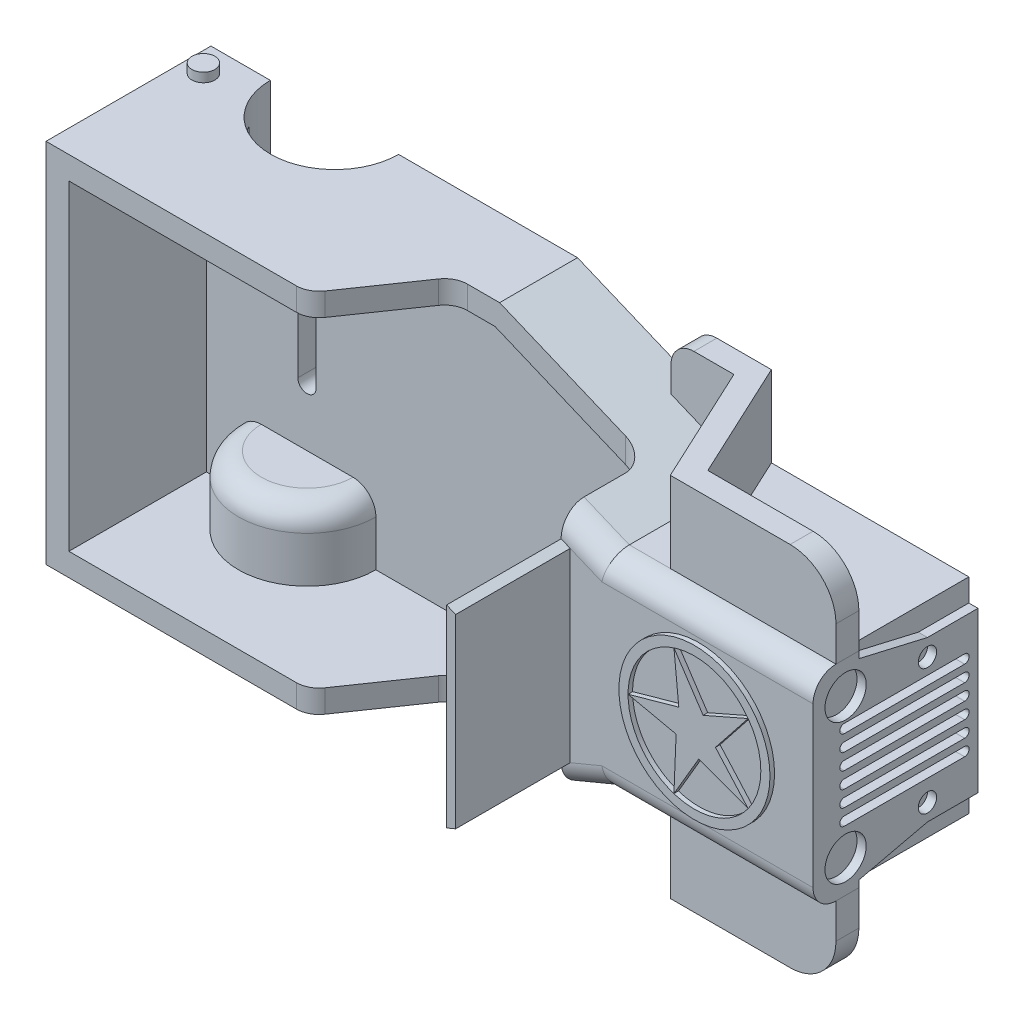
SolidWorks part; units mm, degrees
ref_plane "Front Plane" through (0, 0, 0) normal (0, 0, 1) x (1, 0, 0)
ref_plane "Top Plane" through (0, 0, 0) normal (0, 1, 0) x (1, 0, 0)
ref_plane "Right Plane" through (0, 0, 0) normal (1, 0, 0) x (0, 0, -1)
sketch "Sketch1" plane through (0, 0, 0) normal (0, 0, 1) x (1, 0, 0)
  line L0 (-30, -40) -> (-30, 40)
  line L1 (-30, 40) -> (50, 40)
  line L2 (50, 40) -> (92.3198, 22.3788)
  line L3 (92.3198, 22.3788) -> (137.4114, 22.3788)
  line L4 (137.4114, 22.3788) -> (137.4114, -22.3788)
  line L6 (92.3198, -22.3788) -> (137.4114, -22.3788)
  line L7 (50, -40) -> (92.3198, -22.3788)
  line L8 (-30, -40) -> (50, -40)
  dimension "D1" = 80
  dimension "D2" = 80
extrude "Boss-Extrude1" add sketch "Sketch1" against normal blind 6
sketch "Sketch2" plane through (0, 0, 0) normal (0, 0, 1) x (1, 0, 0)
  line L0 (82.4322, 26.4958) -> (82.4322, -26.4958)
  line L8 (137.4114, 22.3788) -> (92.3198, 22.3788)
  line L9 (92.3198, 22.3788) -> (50, 40)
  line L10 (50, 40) -> (-30, 40)
  line L11 (-30, 40) -> (-30, -40)
  line L12 (-30, -40) -> (50, -40)
  line L13 (50, -40) -> (92.3198, -22.3788)
  line L14 (92.3198, -22.3788) -> (137.4114, -22.3788)
  line L15 (137.4114, -22.3788) -> (137.4114, 22.3788)
  line L16 (137.4114, 22.3788) -> (92.3198, 22.3788)
  line L17 (92.3198, 22.3788) -> (82.4322, 26.4958)
  line L21 (82.4322, -26.4958) -> (92.3198, -22.3788)
  line L22 (92.3198, -22.3788) -> (137.4114, -22.3788)
  line L23 (137.4114, -22.3788) -> (137.4114, 22.3788)
  dimension "D1" = 0
extrude "Boss-Extrude2" add sketch "Sketch2" along normal blind 30
fillet "Fillet1" radius 5 4 edges at (114.8656, 22.3788, 30) (114.8656, -22.3788, 30) (87.376, 24.4373, 30) (87.376, -24.4373, 30)
shell "Shell1" thickness 5 removed face at (82.4322, 4.416, 22.8452)
sketch "Sketch3" plane through (0, 0, 0) normal (0, 0, 1) x (1, 0, 0)
  line L8 (82.4322, 21.0797) -> (82.4322, 26.4958)
  line L9 (82.4322, 26.4958) -> (50, 40)
  line L10 (50, 40) -> (-30, 40)
  line L11 (-30, 40) -> (-30, -40)
  line L12 (-30, -40) -> (50, -40)
  line L13 (50, -40) -> (82.4322, -26.4958)
  line L14 (82.4322, -26.4958) -> (82.4322, -21.0797)
  line L15 (82.4322, -21.0797) -> (82.4322, 21.0797)
  line L16 (82.4322, 21.0797) -> (82.4322, 26.4958)
  line L17 (82.4322, 26.4958) -> (50, 40)
  line L18 (50, 40) -> (-30, 40)
  line L19 (-30, 40) -> (-30, -40)
  line L20 (-30, -40) -> (50, -40)
  line L21 (50, -40) -> (82.4322, -26.4958)
  line L22 (82.4322, -26.4958) -> (82.4322, -21.0797)
  line L40 (77.4322, 21.0797) -> (77.4322, 23.1616)
  line L41 (77.4322, 23.1616) -> (49.0006, 35)
  line L42 (49.0006, 35) -> (-25, 35)
  line L43 (-25, 35) -> (-25, -35)
  line L44 (-25, -35) -> (49.0006, -35)
  line L45 (49.0006, -35) -> (77.4322, -23.1616)
  line L46 (77.4322, -23.1616) -> (77.4322, -21.0797)
  line L47 (77.4322, -21.0797) -> (77.4322, 21.0797)
  line L49 (82.4322, 21.0797) -> (49.0006, 35)
  line L50 (49.0006, 35) -> (-25, 35)
  line L51 (-25, 35) -> (-25, -35)
  line L52 (-25, -35) -> (49.0006, -35)
  line L53 (49.0006, -35) -> (82.4322, -21.0797)
  dimension "D1" = 0
  dimension "D2" = 5
extrude "Boss-Extrude3" add sketch "Sketch3" along normal blind 30
sketch "Sketch4" plane through (0, 0, 0) normal (0, 1, 0) x (1, 0, 0)
  line L0 (82.4322, -30) -> (82.4322, -11)
  line L1 (82.4322, -11) -> (40.3506, -11)
  line L2 (40.3506, -11) -> (27.2574, -30)
  line L3 (-30, -30) -> (50, -30) construction
  line L4 (27.2574, -30) -> (82.4322, -30)
extrude "Cut-Extrude1" cut sketch "Sketch4" against normal through all both and the other way through all
fillet "Fillet2" radius 5 6 edges at (82.4322, -23.7877, 11) (82.4322, 23.7877, 11) (40.3506, -37.5, 11) (40.3506, 37.5, 11) (27.2574, -37.5, 30) (27.2574, 37.5, 30)
sketch "Sketch10" plane through (0, 35, 0) normal (0, -1, 0) x (1, 0, 0)
  line L0 (-25, 0) -> (49.0006, 0) construction
  line L1 (-17.9963, 0) -> (-15.9963, 0)
  line L2 (10.0037, 0) -> (12.0037, 0)
  arc A0 (-15.9963, 0) -> (10.0037, 0) centre (-2.9963, 0) cw
  arc A1 (-17.9963, 0) -> (12.0037, 0) centre (-2.9963, 0) cw
  dimension "D1" = 13
  dimension "D2" = 2
extrude "Boss-Extrude8" add sketch "Sketch10" along normal blind 15
sketch "Sketch13" plane through (0, 40, 0) normal (0, 1, 0) x (1, 0, 0)
  line L0 (10.9614, 6.063) -> (-17.0386, 6.063)
  arc A2 (-17.0386, 6.063) -> (10.9614, 6.063) centre (-3.0386, 6.063) ccw
extrude "Cut-Extrude4" cut sketch "Sketch13" against normal blind 15
sketch "Sketch14" plane through (0, 20, 0) normal (0, -1, 0) x (1, 0, 0)
  line L0 (-15.9963, 0) -> (10.0037, 0)
  arc A0 (10.0037, 0) -> (-15.9963, 0) centre (-2.9963, 0) ccw construction
  arc A1 (10.0037, 0) -> (-15.9963, 0) centre (-2.9963, 0) ccw
extrude "Boss-Extrude10" add sketch "Sketch14" against normal up to vertex (5 mm away) up to point (-15.6576, 25, 0)
fillet "Fillet3" radius 5 1 edges at (-2.9963, 20, 15)
mirror "Mirror1" about plane through (0, 0, 0) normal (0, 1, 0) of "Fillet3", "Boss-Extrude10", "Boss-Extrude8", "Cut-Extrude4"
sketch "Sketch15" plane through (0, -40, 0) normal (0, -1, 0) x (1, 0, 0)
  line L0 (137.4114, 20) -> (104.4438, 20)
  line L1 (137.4114, -6) -> (137.4114, 25) construction
  line L2 (104.4438, 20) -> (92.3198, -6)
  line L3 (92.3198, -6) -> (75.4114, -6)
  line L4 (50, -6) -> (92.3198, -6) construction
  line L5 (137.4114, 25) -> (137.4114, 20)
  line L6 (137.4114, 25) -> (101.2584, 25)
  line L7 (101.2584, 25) -> (89.1344, -1)
  line L8 (89.1344, -1) -> (75.4114, -1)
  line L9 (75.4114, -1) -> (75.4114, -6)
  dimension "D1" = 115
  dimension "D2" = 26
  dimension "D3" = 62
  dimension "D4" = 16.9084
  dimension "D5" = 5
extrude "Boss-Extrude11" add sketch "Sketch15" against normal up to next separate body
fillet "Fillet4" radius 5 1 edges at (75.4114, -40, -3.5)
fillet "Fillet5" radius 10 1 edges at (137.4114, -40, 22.5)
mirror "Mirror6" about plane through (0, 0, 0) normal (0, 1, 0) of bodies 115
sketch "Sketch16" plane through (137.4114, 0, 0) normal (1, 0, 0) x (0, 0, -1)
  line L0 (-30, 0) -> (6, 0) construction
  line L1 (-30, -17.3788) -> (-30, 17.3788) construction
  line L2 (6, -22.3788) -> (6, 22.3788) construction
  line L4 (-20, -22.3788) -> (-20, -20.9143)
  line L5 (-20, -20.9143) -> (-5.0256, -17.436)
  line L6 (-5.0256, -17.436) -> (6, -17.436)
  line L7 (6, -17.436) -> (6, -22.3788)
  line L8 (6, -22.3788) -> (-20, -22.3788)
  circle A1 centre (-22.8997, -15.2785) radius 4.5
  circle A2 centre (-5.0256, -13.7435) radius 2
  dimension "D1" = 4
  dimension "D2" = 9
extrude "Cut-Extrude5" cut sketch "Sketch16" against normal blind 2
mirror "Mirror7" about plane through (0, 0, 0) normal (0, 1, 0) of "Cut-Extrude5"
sketch "Sketch17" plane through (137.4114, 0, 0) normal (1, 0, 0) x (0, 0, -1)
  line L0 (-23.1915, -8.1908) -> (3.0841, -8.1908) construction
  line L1 (-23.1915, -7.2177) -> (3.0841, -7.2177)
  line L2 (-23.1915, -9.164) -> (3.0841, -9.164)
  arc A0 (-23.1915, -7.2177) -> (-23.1915, -9.164) centre (-23.1915, -8.1908) ccw
  arc A1 (3.0841, -9.164) -> (3.0841, -7.2177) centre (3.0841, -8.1908) ccw
  point P2 (-10.0537, -8.1908)
extrude "Cut-Extrude6" cut sketch "Sketch17" against normal blind 2
pattern_linear "LPattern1" count 6 spacing 3.5 along (0, 1, 0) of "Cut-Extrude6"
sketch "Sketch18" plane through (0, 0, -6) normal (0, 0, -1) x (-1, 0, 0)
  line L4 (1.0386, -7.2126) -> (1.0386, 7.2126)
  line L5 (5.0386, -7.2126) -> (5.0386, 7.2126)
  line L14 (-108.4499, -7.2126) -> (-108.4499, 7.2126)
  line L15 (-112.4499, -7.2126) -> (-112.4499, 7.2126)
  arc A0 (1.0386, -7.2126) -> (5.0386, -7.2126) centre (3.0386, -7.2126) ccw
  arc A1 (5.0386, 7.2126) -> (1.0386, 7.2126) centre (3.0386, 7.2126) ccw
  arc A2 (-108.4499, -7.2126) -> (-112.4499, -7.2126) centre (-110.4499, -7.2126) cw
  arc A3 (-112.4499, 7.2126) -> (-108.4499, 7.2126) centre (-110.4499, 7.2126) cw
  point P8 (3.0386, 0)
  point P29 (-110.4499, 0)
  dimension "D1" = 2
extrude "Cut-Extrude7" cut sketch "Sketch18" against normal blind 15
sketch "Sketch19" plane through (0, -40, 0) normal (0, -1, 0) x (1, 0, 0)
  circle A0 centre (-25.6454, 0) radius 2.5
  dimension "D1" = 5
extrude "Boss-Extrude12" add sketch "Sketch19" along normal blind 2
sketch "Sketch20" plane through (-30, 0, 0) normal (-1, 0, 0) x (0, 0, 1)
  circle A0 centre (0, 34.3281) radius 3
  circle A1 centre (0, 25.5168) radius 3
  circle A2 centre (6.015, 29.9225) radius 2
  dimension "D1" = 6
  dimension "D2" = 6
  dimension "D3" = 4
extrude "Boss-Extrude13" add sketch "Sketch20" along normal blind 2
mirror "Mirror8" about plane through (0, 0, 0) normal (0, 1, 0) of "Boss-Extrude12", "Boss-Extrude13"
sketch "Sketch21" plane through (0, 0, 30) normal (0, 0, 1) x (1, 0, 0)
  line L0 (108.0476, 13.7797) -> (114.4162, 4.2075)
  line L1 (114.4162, 4.2075) -> (124.2501, 8.5114)
  line L2 (124.2465, 8.5163) -> (117.1109, -0.4986)
  line L3 (98.0361, 0) -> (109.1077, 3.0989)
  line L4 (109.1077, 3.0989) -> (108.0533, 13.7815)
  line L5 (117.1109, -0.4986) -> (124.243, -8.5212)
  line L6 (124.2465, -8.5163) -> (113.4679, -4.5156)
  line L7 (113.4679, -4.5156) -> (108.0418, -13.7778)
  line L8 (108.0476, -13.7797) -> (108.5216, -2.2923)
  line L9 (108.5216, -2.2923) -> (98.0361, 0.0061)
  circle A0 centre (112.5248, 0) radius 16.4888
  circle A1 centre (112.5248, 0) radius 14.4888
  point P22 (112.5248, 0)
  dimension "D2" = 100
  dimension "D1" = 2
  dimension "D3" = 5
extrude "Boss-Extrude14" add sketch "Sketch21" along normal blind 1 contours A0 A1 | L9 L8 L7 L6 L5 L2 L1 L0 L4 L3 region at (112.5248, 0, 30) region at (96.5024, 0, 30)
sketch "Sketch22" plane through (0, 0, 30) normal (0, 0, 1) x (1, 0, 0)
  line L0 (91.3204, 17.3788) -> (82.4322, 21.0797) construction
  line L1 (82.4322, 21.0797) -> (82.4322, -21.0797) construction
  line L2 (82.4322, -21.0797) -> (91.3204, -17.3788) construction
  line L3 (84.4077, 20.2571) -> (82.4322, 21.0797)
  line L4 (82.4322, 21.0797) -> (82.4322, 18.9776)
  line L5 (82.4322, -21.0797) -> (84.4077, -20.2571)
  line L6 (84.4077, -20.2571) -> (84.4077, -18.9776)
  line L7 (84.4077, 18.9776) -> (82.4322, 18.9776)
  line L8 (84.4077, 18.9776) -> (84.4077, 20.2571)
  line L9 (84.4077, -18.9776) -> (82.4322, -18.9776)
  line L10 (82.4322, -18.9776) -> (82.4322, -21.0797)
extrude "Boss-Extrude15" add sketch "Sketch22" along normal blind 25
sketch "Sketch23" plane through (0, -18.9776, 0) normal (0, 1, 0) x (1, 0, 0)
  line L0 (82.4322, -55) -> (82.4322, -30) construction
  line L1 (84.4077, -55) -> (82.4322, -55)
  line L2 (84.4077, -55) -> (84.4077, -53.2321)
  line L3 (84.4077, -53.2321) -> (82.4322, -53.2321)
  line L4 (82.4322, -55) -> (82.4322, -53.2321)
extrude "Boss-Extrude16" add sketch "Sketch23" along normal up to next
sketch "Sketch25" plane through (0, -18.9776, 0) normal (0, 1, 0) x (1, 0, 0)
  line L0 (82.4322, -53.2321) -> (82.4322, -30) construction
  line L1 (84.4077, -30) -> (82.4322, -30)
  line L2 (84.4077, -30) -> (84.4077, -31.0284)
  line L3 (84.4077, -31.0284) -> (82.4322, -31.0284)
  line L4 (82.4322, -30) -> (82.4322, -31.0284)
extrude "Boss-Extrude17" add sketch "Sketch25" along normal up to next
sketch "Sketch26" plane through (84.4077, 0, 0) normal (1, 0, 0) x (0, 0, -1)
  line L0 (-53.2321, 18.9776) -> (-31.0284, 18.9776) construction
  line L1 (-53.2321, 18.9776) -> (-53.2321, -18.9776) construction
  line L2 (-53.2321, -18.9776) -> (-31.0284, -18.9776) construction
  line L3 (-31.0284, 18.9776) -> (-31.0284, -18.9776) construction
  line L4 (-53.2321, 18.9776) -> (-31.0284, 18.9776)
  line L5 (-53.2321, 18.9776) -> (-53.2321, -18.9776)
  line L6 (-53.2321, -18.9776) -> (-31.0284, -18.9776)
  line L7 (-31.0284, 18.9776) -> (-31.0284, -18.9776)
extrude "Boss-Extrude25" add sketch "Sketch26" against normal blind 2
sketch "Sketch27" plane through (-30, 0, 0) normal (-1, 0, 0) x (0, 0, 1)
  circle A0 centre (12, 0) radius 2.5
  dimension "D1" = 5
extrude "Boss-Extrude26" add sketch "Sketch27" along normal blind 11
fillet "Fillet6" radius 1 1 edges at (-41, 0, 14.5)
